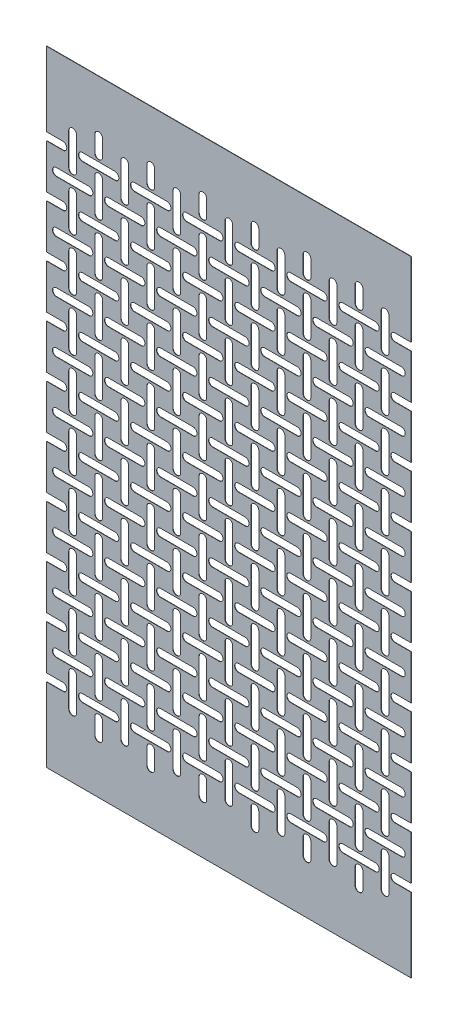
SolidWorks part; units mm, degrees
ref_plane "Front Plane" through (0, 0, 0) normal (0, 0, 1) x (1, 0, 0)
ref_plane "Top Plane" through (0, 0, 0) normal (0, 1, 0) x (1, 0, 0)
ref_plane "Right Plane" through (0, 0, 0) normal (1, 0, 0) x (0, 0, -1)
sketch "Model" plane through (0, 0, 0) normal (0, 0, 1) x (1, 0, 0)
  line L0 (0, 31.5) -> (6.25, 31.5)
  line L1 (0, 28.5) -> (6.25, 28.5)
  line L2 (13.75, 31.5) -> (26.25, 31.5)
  line L3 (13.75, 28.5) -> (26.25, 28.5)
  line L4 (33.75, 31.5) -> (46.25, 31.5)
  line L5 (33.75, 28.5) -> (46.25, 28.5)
  line L6 (53.75, 31.5) -> (66.25, 31.5)
  line L7 (53.75, 28.5) -> (66.25, 28.5)
  line L8 (73.75, 31.5) -> (86.25, 31.5)
  line L9 (73.75, 28.5) -> (86.25, 28.5)
  line L10 (93.75, 31.5) -> (106.25, 31.5)
  line L11 (93.75, 28.5) -> (106.25, 28.5)
  line L12 (113.75, 31.5) -> (126.25, 31.5)
  line L13 (113.75, 28.5) -> (126.25, 28.5)
  line L14 (133.75, 31.5) -> (140, 31.5)
  line L15 (133.75, 28.5) -> (140, 28.5)
  line L16 (3.75, 41.5) -> (16.25, 41.5)
  line L17 (3.75, 38.5) -> (16.25, 38.5)
  line L18 (23.75, 41.5) -> (36.25, 41.5)
  line L19 (23.75, 38.5) -> (36.25, 38.5)
  line L20 (43.75, 41.5) -> (56.25, 41.5)
  line L21 (43.75, 38.5) -> (56.25, 38.5)
  line L22 (63.75, 41.5) -> (76.25, 41.5)
  line L23 (63.75, 38.5) -> (76.25, 38.5)
  line L24 (83.75, 41.5) -> (96.25, 41.5)
  line L25 (83.75, 38.5) -> (96.25, 38.5)
  line L26 (103.75, 41.5) -> (116.25, 41.5)
  line L27 (103.75, 38.5) -> (116.25, 38.5)
  line L28 (123.75, 41.5) -> (136.25, 41.5)
  line L29 (123.75, 38.5) -> (136.25, 38.5)
  line L30 (0, 51.5) -> (6.25, 51.5)
  line L31 (0, 48.5) -> (6.25, 48.5)
  line L32 (13.75, 51.5) -> (26.25, 51.5)
  line L33 (13.75, 48.5) -> (26.25, 48.5)
  line L34 (33.75, 51.5) -> (46.25, 51.5)
  line L35 (33.75, 48.5) -> (46.25, 48.5)
  line L36 (53.75, 51.5) -> (66.25, 51.5)
  line L37 (53.75, 48.5) -> (66.25, 48.5)
  line L38 (73.75, 51.5) -> (86.25, 51.5)
  line L39 (73.75, 48.5) -> (86.25, 48.5)
  line L40 (93.75, 51.5) -> (106.25, 51.5)
  line L41 (93.75, 48.5) -> (106.25, 48.5)
  line L42 (113.75, 51.5) -> (126.25, 51.5)
  line L43 (113.75, 48.5) -> (126.25, 48.5)
  line L44 (133.75, 51.5) -> (140, 51.5)
  line L45 (133.75, 48.5) -> (140, 48.5)
  line L46 (3.75, 61.5) -> (16.25, 61.5)
  line L47 (3.75, 58.5) -> (16.25, 58.5)
  line L48 (23.75, 61.5) -> (36.25, 61.5)
  line L49 (23.75, 58.5) -> (36.25, 58.5)
  line L50 (43.75, 61.5) -> (56.25, 61.5)
  line L51 (43.75, 58.5) -> (56.25, 58.5)
  line L52 (63.75, 61.5) -> (76.25, 61.5)
  line L53 (63.75, 58.5) -> (76.25, 58.5)
  line L54 (83.75, 61.5) -> (96.25, 61.5)
  line L55 (83.75, 58.5) -> (96.25, 58.5)
  line L56 (103.75, 61.5) -> (116.25, 61.5)
  line L57 (103.75, 58.5) -> (116.25, 58.5)
  line L58 (123.75, 61.5) -> (136.25, 61.5)
  line L59 (123.75, 58.5) -> (136.25, 58.5)
  line L60 (0, 71.5) -> (6.25, 71.5)
  line L61 (0, 68.5) -> (6.25, 68.5)
  line L62 (13.75, 71.5) -> (26.25, 71.5)
  line L63 (13.75, 68.5) -> (26.25, 68.5)
  line L64 (33.75, 71.5) -> (46.25, 71.5)
  line L65 (33.75, 68.5) -> (46.25, 68.5)
  line L66 (53.75, 71.5) -> (66.25, 71.5)
  line L67 (53.75, 68.5) -> (66.25, 68.5)
  line L68 (73.75, 71.5) -> (86.25, 71.5)
  line L69 (73.75, 68.5) -> (86.25, 68.5)
  line L70 (93.75, 71.5) -> (106.25, 71.5)
  line L71 (93.75, 68.5) -> (106.25, 68.5)
  line L72 (113.75, 71.5) -> (126.25, 71.5)
  line L73 (113.75, 68.5) -> (126.25, 68.5)
  line L74 (133.75, 71.5) -> (140, 71.5)
  line L75 (133.75, 68.5) -> (140, 68.5)
  line L76 (3.75, 81.5) -> (16.25, 81.5)
  line L77 (3.75, 78.5) -> (16.25, 78.5)
  line L78 (23.75, 81.5) -> (36.25, 81.5)
  line L79 (23.75, 78.5) -> (36.25, 78.5)
  line L80 (43.75, 81.5) -> (56.25, 81.5)
  line L81 (43.75, 78.5) -> (56.25, 78.5)
  line L82 (63.75, 81.5) -> (76.25, 81.5)
  line L83 (63.75, 78.5) -> (76.25, 78.5)
  line L84 (83.75, 81.5) -> (96.25, 81.5)
  line L85 (83.75, 78.5) -> (96.25, 78.5)
  line L86 (103.75, 81.5) -> (116.25, 81.5)
  line L87 (103.75, 78.5) -> (116.25, 78.5)
  line L88 (123.75, 81.5) -> (136.25, 81.5)
  line L89 (123.75, 78.5) -> (136.25, 78.5)
  line L90 (0, 91.5) -> (6.25, 91.5)
  line L91 (0, 88.5) -> (6.25, 88.5)
  line L92 (13.75, 91.5) -> (26.25, 91.5)
  line L93 (13.75, 88.5) -> (26.25, 88.5)
  line L94 (33.75, 91.5) -> (46.25, 91.5)
  line L95 (33.75, 88.5) -> (46.25, 88.5)
  line L96 (53.75, 91.5) -> (66.25, 91.5)
  line L97 (53.75, 88.5) -> (66.25, 88.5)
  line L98 (73.75, 91.5) -> (86.25, 91.5)
  line L99 (73.75, 88.5) -> (86.25, 88.5)
  line L100 (93.75, 91.5) -> (106.25, 91.5)
  line L101 (93.75, 88.5) -> (106.25, 88.5)
  line L102 (113.75, 91.5) -> (126.25, 91.5)
  line L103 (113.75, 88.5) -> (126.25, 88.5)
  line L104 (133.75, 91.5) -> (140, 91.5)
  line L105 (133.75, 88.5) -> (140, 88.5)
  line L106 (3.75, 101.5) -> (16.25, 101.5)
  line L107 (3.75, 98.5) -> (16.25, 98.5)
  line L108 (23.75, 101.5) -> (36.25, 101.5)
  line L109 (23.75, 98.5) -> (36.25, 98.5)
  line L110 (43.75, 101.5) -> (56.25, 101.5)
  line L111 (43.75, 98.5) -> (56.25, 98.5)
  line L112 (63.75, 101.5) -> (76.25, 101.5)
  line L113 (63.75, 98.5) -> (76.25, 98.5)
  line L114 (83.75, 101.5) -> (96.25, 101.5)
  line L115 (83.75, 98.5) -> (96.25, 98.5)
  line L116 (103.75, 101.5) -> (116.25, 101.5)
  line L117 (103.75, 98.5) -> (116.25, 98.5)
  line L118 (123.75, 101.5) -> (136.25, 101.5)
  line L119 (123.75, 98.5) -> (136.25, 98.5)
  line L120 (0, 111.5) -> (6.25, 111.5)
  line L121 (0, 108.5) -> (6.25, 108.5)
  line L122 (13.75, 111.5) -> (26.25, 111.5)
  line L123 (13.75, 108.5) -> (26.25, 108.5)
  line L124 (33.75, 111.5) -> (46.25, 111.5)
  line L125 (33.75, 108.5) -> (46.25, 108.5)
  line L126 (53.75, 111.5) -> (66.25, 111.5)
  line L127 (53.75, 108.5) -> (66.25, 108.5)
  line L128 (73.75, 111.5) -> (86.25, 111.5)
  line L129 (73.75, 108.5) -> (86.25, 108.5)
  line L130 (93.75, 111.5) -> (106.25, 111.5)
  line L131 (93.75, 108.5) -> (106.25, 108.5)
  line L132 (113.75, 111.5) -> (126.25, 111.5)
  line L133 (113.75, 108.5) -> (126.25, 108.5)
  line L134 (133.75, 111.5) -> (140, 111.5)
  line L135 (133.75, 108.5) -> (140, 108.5)
  line L136 (3.75, 121.5) -> (16.25, 121.5)
  line L137 (3.75, 118.5) -> (16.25, 118.5)
  line L138 (23.75, 121.5) -> (36.25, 121.5)
  line L139 (23.75, 118.5) -> (36.25, 118.5)
  line L140 (43.75, 121.5) -> (56.25, 121.5)
  line L141 (43.75, 118.5) -> (56.25, 118.5)
  line L142 (63.75, 121.5) -> (76.25, 121.5)
  line L143 (63.75, 118.5) -> (76.25, 118.5)
  line L144 (83.75, 121.5) -> (96.25, 121.5)
  line L145 (83.75, 118.5) -> (96.25, 118.5)
  line L146 (103.75, 121.5) -> (116.25, 121.5)
  line L147 (103.75, 118.5) -> (116.25, 118.5)
  line L148 (123.75, 121.5) -> (136.25, 121.5)
  line L149 (123.75, 118.5) -> (136.25, 118.5)
  line L150 (0, 131.5) -> (6.25, 131.5)
  line L151 (0, 128.5) -> (6.25, 128.5)
  line L152 (13.75, 131.5) -> (26.25, 131.5)
  line L153 (13.75, 128.5) -> (26.25, 128.5)
  line L154 (33.75, 131.5) -> (46.25, 131.5)
  line L155 (33.75, 128.5) -> (46.25, 128.5)
  line L156 (53.75, 131.5) -> (66.25, 131.5)
  line L157 (53.75, 128.5) -> (66.25, 128.5)
  line L158 (73.75, 131.5) -> (86.25, 131.5)
  line L159 (73.75, 128.5) -> (86.25, 128.5)
  line L160 (93.75, 131.5) -> (106.25, 131.5)
  line L161 (93.75, 128.5) -> (106.25, 128.5)
  line L162 (113.75, 131.5) -> (126.25, 131.5)
  line L163 (113.75, 128.5) -> (126.25, 128.5)
  line L164 (133.75, 131.5) -> (140, 131.5)
  line L165 (133.75, 128.5) -> (140, 128.5)
  line L166 (3.75, 141.5) -> (16.25, 141.5)
  line L167 (3.75, 138.5) -> (16.25, 138.5)
  line L168 (23.75, 141.5) -> (36.25, 141.5)
  line L169 (23.75, 138.5) -> (36.25, 138.5)
  line L170 (43.75, 141.5) -> (56.25, 141.5)
  line L171 (43.75, 138.5) -> (56.25, 138.5)
  line L172 (63.75, 141.5) -> (76.25, 141.5)
  line L173 (63.75, 138.5) -> (76.25, 138.5)
  line L174 (83.75, 141.5) -> (96.25, 141.5)
  line L175 (83.75, 138.5) -> (96.25, 138.5)
  line L176 (103.75, 141.5) -> (116.25, 141.5)
  line L177 (103.75, 138.5) -> (116.25, 138.5)
  line L178 (123.75, 141.5) -> (136.25, 141.5)
  line L179 (123.75, 138.5) -> (136.25, 138.5)
  line L180 (0, 151.5) -> (6.25, 151.5)
  line L181 (0, 148.5) -> (6.25, 148.5)
  line L182 (13.75, 151.5) -> (26.25, 151.5)
  line L183 (13.75, 148.5) -> (26.25, 148.5)
  line L184 (33.75, 151.5) -> (46.25, 151.5)
  line L185 (33.75, 148.5) -> (46.25, 148.5)
  line L186 (53.75, 151.5) -> (66.25, 151.5)
  line L187 (53.75, 148.5) -> (66.25, 148.5)
  line L188 (73.75, 151.5) -> (86.25, 151.5)
  line L189 (73.75, 148.5) -> (86.25, 148.5)
  line L190 (93.75, 151.5) -> (106.25, 151.5)
  line L191 (93.75, 148.5) -> (106.25, 148.5)
  line L192 (113.75, 151.5) -> (126.25, 151.5)
  line L193 (113.75, 148.5) -> (126.25, 148.5)
  line L194 (133.75, 151.5) -> (140, 151.5)
  line L195 (133.75, 148.5) -> (140, 148.5)
  line L196 (3.75, 161.5) -> (16.25, 161.5)
  line L197 (3.75, 158.5) -> (16.25, 158.5)
  line L198 (23.75, 161.5) -> (36.25, 161.5)
  line L199 (23.75, 158.5) -> (36.25, 158.5)
  line L200 (43.75, 161.5) -> (56.25, 161.5)
  line L201 (43.75, 158.5) -> (56.25, 158.5)
  line L202 (63.75, 161.5) -> (76.25, 161.5)
  line L203 (63.75, 158.5) -> (76.25, 158.5)
  line L204 (83.75, 161.5) -> (96.25, 161.5)
  line L205 (83.75, 158.5) -> (96.25, 158.5)
  line L206 (103.75, 161.5) -> (116.25, 161.5)
  line L207 (103.75, 158.5) -> (116.25, 158.5)
  line L208 (123.75, 161.5) -> (136.25, 161.5)
  line L209 (123.75, 158.5) -> (136.25, 158.5)
  line L210 (0, 171.5) -> (6.25, 171.5)
  line L211 (0, 168.5) -> (6.25, 168.5)
  line L212 (13.75, 171.5) -> (26.25, 171.5)
  line L213 (13.75, 168.5) -> (26.25, 168.5)
  line L214 (33.75, 171.5) -> (46.25, 171.5)
  line L215 (33.75, 168.5) -> (46.25, 168.5)
  line L216 (53.75, 171.5) -> (66.25, 171.5)
  line L217 (53.75, 168.5) -> (66.25, 168.5)
  line L218 (73.75, 171.5) -> (86.25, 171.5)
  line L219 (73.75, 168.5) -> (86.25, 168.5)
  line L220 (93.75, 171.5) -> (106.25, 171.5)
  line L221 (93.75, 168.5) -> (106.25, 168.5)
  line L222 (113.75, 171.5) -> (126.25, 171.5)
  line L223 (113.75, 168.5) -> (126.25, 168.5)
  line L224 (133.75, 171.5) -> (140, 171.5)
  line L225 (133.75, 168.5) -> (140, 168.5)
  line L226 (3.75, 181.5) -> (16.25, 181.5)
  line L227 (3.75, 178.5) -> (16.25, 178.5)
  line L228 (23.75, 181.5) -> (36.25, 181.5)
  line L229 (23.75, 178.5) -> (36.25, 178.5)
  line L230 (43.75, 181.5) -> (56.25, 181.5)
  line L231 (43.75, 178.5) -> (56.25, 178.5)
  line L232 (63.75, 181.5) -> (76.25, 181.5)
  line L233 (63.75, 178.5) -> (76.25, 178.5)
  line L234 (83.75, 181.5) -> (96.25, 181.5)
  line L235 (83.75, 178.5) -> (96.25, 178.5)
  line L236 (103.75, 181.5) -> (116.25, 181.5)
  line L237 (103.75, 178.5) -> (116.25, 178.5)
  line L238 (123.75, 181.5) -> (136.25, 181.5)
  line L239 (123.75, 178.5) -> (136.25, 178.5)
  line L240 (0, 191.5) -> (6.25, 191.5)
  line L241 (0, 188.5) -> (6.25, 188.5)
  line L242 (13.75, 191.5) -> (26.25, 191.5)
  line L243 (13.75, 188.5) -> (26.25, 188.5)
  line L244 (33.75, 191.5) -> (46.25, 191.5)
  line L245 (33.75, 188.5) -> (46.25, 188.5)
  line L246 (53.75, 191.5) -> (66.25, 191.5)
  line L247 (53.75, 188.5) -> (66.25, 188.5)
  line L248 (73.75, 191.5) -> (86.25, 191.5)
  line L249 (73.75, 188.5) -> (86.25, 188.5)
  line L250 (93.75, 191.5) -> (106.25, 191.5)
  line L251 (93.75, 188.5) -> (106.25, 188.5)
  line L252 (113.75, 191.5) -> (126.25, 191.5)
  line L253 (113.75, 188.5) -> (126.25, 188.5)
  line L254 (133.75, 191.5) -> (140, 191.5)
  line L255 (133.75, 188.5) -> (140, 188.5)
  line L256 (3.75, 201.5) -> (16.25, 201.5)
  line L257 (3.75, 198.5) -> (16.25, 198.5)
  line L258 (23.75, 201.5) -> (36.25, 201.5)
  line L259 (23.75, 198.5) -> (36.25, 198.5)
  line L260 (43.75, 201.5) -> (56.25, 201.5)
  line L261 (43.75, 198.5) -> (56.25, 198.5)
  line L262 (63.75, 201.5) -> (76.25, 201.5)
  line L263 (63.75, 198.5) -> (76.25, 198.5)
  line L264 (83.75, 201.5) -> (96.25, 201.5)
  line L265 (83.75, 198.5) -> (96.25, 198.5)
  line L266 (103.75, 201.5) -> (116.25, 201.5)
  line L267 (103.75, 198.5) -> (116.25, 198.5)
  line L268 (123.75, 201.5) -> (136.25, 201.5)
  line L269 (123.75, 198.5) -> (136.25, 198.5)
  line L270 (0, 211.5) -> (6.25, 211.5)
  line L271 (0, 208.5) -> (6.25, 208.5)
  line L272 (13.75, 211.5) -> (26.25, 211.5)
  line L273 (13.75, 208.5) -> (26.25, 208.5)
  line L274 (33.75, 211.5) -> (46.25, 211.5)
  line L275 (33.75, 208.5) -> (46.25, 208.5)
  line L276 (53.75, 211.5) -> (66.25, 211.5)
  line L277 (53.75, 208.5) -> (66.25, 208.5)
  line L278 (73.75, 211.5) -> (86.25, 211.5)
  line L279 (73.75, 208.5) -> (86.25, 208.5)
  line L280 (93.75, 211.5) -> (106.25, 211.5)
  line L281 (93.75, 208.5) -> (106.25, 208.5)
  line L282 (113.75, 211.5) -> (126.25, 211.5)
  line L283 (113.75, 208.5) -> (126.25, 208.5)
  line L284 (133.75, 211.5) -> (140, 211.5)
  line L285 (133.75, 208.5) -> (140, 208.5)
  line L286 (11.5, 23.75) -> (11.5, 36.25)
  line L287 (8.5, 23.75) -> (8.5, 36.25)
  line L288 (11.5, 43.75) -> (11.5, 56.25)
  line L289 (8.5, 43.75) -> (8.5, 56.25)
  line L290 (11.5, 63.75) -> (11.5, 76.25)
  line L291 (8.5, 63.75) -> (8.5, 76.25)
  line L292 (11.5, 83.75) -> (11.5, 96.25)
  line L293 (8.5, 83.75) -> (8.5, 96.25)
  line L294 (11.5, 103.75) -> (11.5, 116.25)
  line L295 (8.5, 103.75) -> (8.5, 116.25)
  line L296 (11.5, 123.75) -> (11.5, 136.25)
  line L297 (8.5, 123.75) -> (8.5, 136.25)
  line L298 (11.5, 143.75) -> (11.5, 156.25)
  line L299 (8.5, 143.75) -> (8.5, 156.25)
  line L300 (11.5, 163.75) -> (11.5, 176.25)
  line L301 (8.5, 163.75) -> (8.5, 176.25)
  line L302 (11.5, 183.75) -> (11.5, 196.25)
  line L303 (8.5, 183.75) -> (8.5, 196.25)
  line L304 (11.5, 203.75) -> (11.5, 216.25)
  line L305 (8.5, 203.75) -> (8.5, 216.25)
  line L306 (21.5, 20) -> (21.5, 26.25)
  line L307 (18.5, 20) -> (18.5, 26.25)
  line L308 (21.5, 33.75) -> (21.5, 46.25)
  line L309 (18.5, 33.75) -> (18.5, 46.25)
  line L310 (21.5, 53.75) -> (21.5, 66.25)
  line L311 (18.5, 53.75) -> (18.5, 66.25)
  line L312 (21.5, 73.75) -> (21.5, 86.25)
  line L313 (18.5, 73.75) -> (18.5, 86.25)
  line L314 (21.5, 93.75) -> (21.5, 106.25)
  line L315 (18.5, 93.75) -> (18.5, 106.25)
  line L316 (21.5, 113.75) -> (21.5, 126.25)
  line L317 (18.5, 113.75) -> (18.5, 126.25)
  line L318 (21.5, 133.75) -> (21.5, 146.25)
  line L319 (18.5, 133.75) -> (18.5, 146.25)
  line L320 (21.5, 153.75) -> (21.5, 166.25)
  line L321 (18.5, 153.75) -> (18.5, 166.25)
  line L322 (21.5, 173.75) -> (21.5, 186.25)
  line L323 (18.5, 173.75) -> (18.5, 186.25)
  line L324 (21.5, 193.75) -> (21.5, 206.25)
  line L325 (18.5, 193.75) -> (18.5, 206.25)
  line L326 (21.5, 213.75) -> (21.5, 220)
  line L327 (18.5, 213.75) -> (18.5, 220)
  line L328 (31.5, 23.75) -> (31.5, 36.25)
  line L329 (28.5, 23.75) -> (28.5, 36.25)
  line L330 (31.5, 43.75) -> (31.5, 56.25)
  line L331 (28.5, 43.75) -> (28.5, 56.25)
  line L332 (31.5, 63.75) -> (31.5, 76.25)
  line L333 (28.5, 63.75) -> (28.5, 76.25)
  line L334 (31.5, 83.75) -> (31.5, 96.25)
  line L335 (28.5, 83.75) -> (28.5, 96.25)
  line L336 (31.5, 103.75) -> (31.5, 116.25)
  line L337 (28.5, 103.75) -> (28.5, 116.25)
  line L338 (31.5, 123.75) -> (31.5, 136.25)
  line L339 (28.5, 123.75) -> (28.5, 136.25)
  line L340 (31.5, 143.75) -> (31.5, 156.25)
  line L341 (28.5, 143.75) -> (28.5, 156.25)
  line L342 (31.5, 163.75) -> (31.5, 176.25)
  line L343 (28.5, 163.75) -> (28.5, 176.25)
  line L344 (31.5, 183.75) -> (31.5, 196.25)
  line L345 (28.5, 183.75) -> (28.5, 196.25)
  line L346 (31.5, 203.75) -> (31.5, 216.25)
  line L347 (28.5, 203.75) -> (28.5, 216.25)
  line L348 (41.5, 20) -> (41.5, 26.25)
  line L349 (38.5, 20) -> (38.5, 26.25)
  line L350 (41.5, 33.75) -> (41.5, 46.25)
  line L351 (38.5, 33.75) -> (38.5, 46.25)
  line L352 (41.5, 53.75) -> (41.5, 66.25)
  line L353 (38.5, 53.75) -> (38.5, 66.25)
  line L354 (41.5, 73.75) -> (41.5, 86.25)
  line L355 (38.5, 73.75) -> (38.5, 86.25)
  line L356 (41.5, 93.75) -> (41.5, 106.25)
  line L357 (38.5, 93.75) -> (38.5, 106.25)
  line L358 (41.5, 113.75) -> (41.5, 126.25)
  line L359 (38.5, 113.75) -> (38.5, 126.25)
  line L360 (41.5, 133.75) -> (41.5, 146.25)
  line L361 (38.5, 133.75) -> (38.5, 146.25)
  line L362 (41.5, 153.75) -> (41.5, 166.25)
  line L363 (38.5, 153.75) -> (38.5, 166.25)
  line L364 (41.5, 173.75) -> (41.5, 186.25)
  line L365 (38.5, 173.75) -> (38.5, 186.25)
  line L366 (41.5, 193.75) -> (41.5, 206.25)
  line L367 (38.5, 193.75) -> (38.5, 206.25)
  line L368 (41.5, 213.75) -> (41.5, 220)
  line L369 (38.5, 213.75) -> (38.5, 220)
  line L370 (51.5, 23.75) -> (51.5, 36.25)
  line L371 (48.5, 23.75) -> (48.5, 36.25)
  line L372 (51.5, 43.75) -> (51.5, 56.25)
  line L373 (48.5, 43.75) -> (48.5, 56.25)
  line L374 (51.5, 63.75) -> (51.5, 76.25)
  line L375 (48.5, 63.75) -> (48.5, 76.25)
  line L376 (51.5, 83.75) -> (51.5, 96.25)
  line L377 (48.5, 83.75) -> (48.5, 96.25)
  line L378 (51.5, 103.75) -> (51.5, 116.25)
  line L379 (48.5, 103.75) -> (48.5, 116.25)
  line L380 (51.5, 123.75) -> (51.5, 136.25)
  line L381 (48.5, 123.75) -> (48.5, 136.25)
  line L382 (51.5, 143.75) -> (51.5, 156.25)
  line L383 (48.5, 143.75) -> (48.5, 156.25)
  line L384 (51.5, 163.75) -> (51.5, 176.25)
  line L385 (48.5, 163.75) -> (48.5, 176.25)
  line L386 (51.5, 183.75) -> (51.5, 196.25)
  line L387 (48.5, 183.75) -> (48.5, 196.25)
  line L388 (51.5, 203.75) -> (51.5, 216.25)
  line L389 (48.5, 203.75) -> (48.5, 216.25)
  line L390 (61.5, 20) -> (61.5, 26.25)
  line L391 (58.5, 20) -> (58.5, 26.25)
  line L392 (61.5, 33.75) -> (61.5, 46.25)
  line L393 (58.5, 33.75) -> (58.5, 46.25)
  line L394 (61.5, 53.75) -> (61.5, 66.25)
  line L395 (58.5, 53.75) -> (58.5, 66.25)
  line L396 (61.5, 73.75) -> (61.5, 86.25)
  line L397 (58.5, 73.75) -> (58.5, 86.25)
  line L398 (61.5, 93.75) -> (61.5, 106.25)
  line L399 (58.5, 93.75) -> (58.5, 106.25)
  line L400 (61.5, 113.75) -> (61.5, 126.25)
  line L401 (58.5, 113.75) -> (58.5, 126.25)
  line L402 (61.5, 133.75) -> (61.5, 146.25)
  line L403 (58.5, 133.75) -> (58.5, 146.25)
  line L404 (61.5, 153.75) -> (61.5, 166.25)
  line L405 (58.5, 153.75) -> (58.5, 166.25)
  line L406 (61.5, 173.75) -> (61.5, 186.25)
  line L407 (58.5, 173.75) -> (58.5, 186.25)
  line L408 (61.5, 193.75) -> (61.5, 206.25)
  line L409 (58.5, 193.75) -> (58.5, 206.25)
  line L410 (61.5, 213.75) -> (61.5, 220)
  line L411 (58.5, 213.75) -> (58.5, 220)
  line L412 (71.5, 23.75) -> (71.5, 36.25)
  line L413 (68.5, 23.75) -> (68.5, 36.25)
  line L414 (71.5, 43.75) -> (71.5, 56.25)
  line L415 (68.5, 43.75) -> (68.5, 56.25)
  line L416 (71.5, 63.75) -> (71.5, 76.25)
  line L417 (68.5, 63.75) -> (68.5, 76.25)
  line L418 (71.5, 83.75) -> (71.5, 96.25)
  line L419 (68.5, 83.75) -> (68.5, 96.25)
  line L420 (71.5, 103.75) -> (71.5, 116.25)
  line L421 (68.5, 103.75) -> (68.5, 116.25)
  line L422 (71.5, 123.75) -> (71.5, 136.25)
  line L423 (68.5, 123.75) -> (68.5, 136.25)
  line L424 (71.5, 143.75) -> (71.5, 156.25)
  line L425 (68.5, 143.75) -> (68.5, 156.25)
  line L426 (71.5, 163.75) -> (71.5, 176.25)
  line L427 (68.5, 163.75) -> (68.5, 176.25)
  line L428 (71.5, 183.75) -> (71.5, 196.25)
  line L429 (68.5, 183.75) -> (68.5, 196.25)
  line L430 (71.5, 203.75) -> (71.5, 216.25)
  line L431 (68.5, 203.75) -> (68.5, 216.25)
  line L432 (81.5, 20) -> (81.5, 26.25)
  line L433 (78.5, 20) -> (78.5, 26.25)
  line L434 (81.5, 33.75) -> (81.5, 46.25)
  line L435 (78.5, 33.75) -> (78.5, 46.25)
  line L436 (81.5, 53.75) -> (81.5, 66.25)
  line L437 (78.5, 53.75) -> (78.5, 66.25)
  line L438 (81.5, 73.75) -> (81.5, 86.25)
  line L439 (78.5, 73.75) -> (78.5, 86.25)
  line L440 (81.5, 93.75) -> (81.5, 106.25)
  line L441 (78.5, 93.75) -> (78.5, 106.25)
  line L442 (81.5, 113.75) -> (81.5, 126.25)
  line L443 (78.5, 113.75) -> (78.5, 126.25)
  line L444 (81.5, 133.75) -> (81.5, 146.25)
  line L445 (78.5, 133.75) -> (78.5, 146.25)
  line L446 (81.5, 153.75) -> (81.5, 166.25)
  line L447 (78.5, 153.75) -> (78.5, 166.25)
  line L448 (81.5, 173.75) -> (81.5, 186.25)
  line L449 (78.5, 173.75) -> (78.5, 186.25)
  line L450 (81.5, 193.75) -> (81.5, 206.25)
  line L451 (78.5, 193.75) -> (78.5, 206.25)
  line L452 (81.5, 213.75) -> (81.5, 220)
  line L453 (78.5, 213.75) -> (78.5, 220)
  line L454 (91.5, 23.75) -> (91.5, 36.25)
  line L455 (88.5, 23.75) -> (88.5, 36.25)
  line L456 (91.5, 43.75) -> (91.5, 56.25)
  line L457 (88.5, 43.75) -> (88.5, 56.25)
  line L458 (91.5, 63.75) -> (91.5, 76.25)
  line L459 (88.5, 63.75) -> (88.5, 76.25)
  line L460 (91.5, 83.75) -> (91.5, 96.25)
  line L461 (88.5, 83.75) -> (88.5, 96.25)
  line L462 (91.5, 103.75) -> (91.5, 116.25)
  line L463 (88.5, 103.75) -> (88.5, 116.25)
  line L464 (91.5, 123.75) -> (91.5, 136.25)
  line L465 (88.5, 123.75) -> (88.5, 136.25)
  line L466 (91.5, 143.75) -> (91.5, 156.25)
  line L467 (88.5, 143.75) -> (88.5, 156.25)
  line L468 (91.5, 163.75) -> (91.5, 176.25)
  line L469 (88.5, 163.75) -> (88.5, 176.25)
  line L470 (91.5, 183.75) -> (91.5, 196.25)
  line L471 (88.5, 183.75) -> (88.5, 196.25)
  line L472 (91.5, 203.75) -> (91.5, 216.25)
  line L473 (88.5, 203.75) -> (88.5, 216.25)
  line L474 (101.5, 20) -> (101.5, 26.25)
  line L475 (98.5, 20) -> (98.5, 26.25)
  line L476 (101.5, 33.75) -> (101.5, 46.25)
  line L477 (98.5, 33.75) -> (98.5, 46.25)
  line L478 (101.5, 53.75) -> (101.5, 66.25)
  line L479 (98.5, 53.75) -> (98.5, 66.25)
  line L480 (101.5, 73.75) -> (101.5, 86.25)
  line L481 (98.5, 73.75) -> (98.5, 86.25)
  line L482 (101.5, 93.75) -> (101.5, 106.25)
  line L483 (98.5, 93.75) -> (98.5, 106.25)
  line L484 (101.5, 113.75) -> (101.5, 126.25)
  line L485 (98.5, 113.75) -> (98.5, 126.25)
  line L486 (101.5, 133.75) -> (101.5, 146.25)
  line L487 (98.5, 133.75) -> (98.5, 146.25)
  line L488 (101.5, 153.75) -> (101.5, 166.25)
  line L489 (98.5, 153.75) -> (98.5, 166.25)
  line L490 (101.5, 173.75) -> (101.5, 186.25)
  line L491 (98.5, 173.75) -> (98.5, 186.25)
  line L492 (101.5, 193.75) -> (101.5, 206.25)
  line L493 (98.5, 193.75) -> (98.5, 206.25)
  line L494 (101.5, 213.75) -> (101.5, 220)
  line L495 (98.5, 213.75) -> (98.5, 220)
  line L496 (111.5, 23.75) -> (111.5, 36.25)
  line L497 (108.5, 23.75) -> (108.5, 36.25)
  line L498 (111.5, 43.75) -> (111.5, 56.25)
  line L499 (108.5, 43.75) -> (108.5, 56.25)
  line L500 (111.5, 63.75) -> (111.5, 76.25)
  line L501 (108.5, 63.75) -> (108.5, 76.25)
  line L502 (111.5, 83.75) -> (111.5, 96.25)
  line L503 (108.5, 83.75) -> (108.5, 96.25)
  line L504 (111.5, 103.75) -> (111.5, 116.25)
  line L505 (108.5, 103.75) -> (108.5, 116.25)
  line L506 (111.5, 123.75) -> (111.5, 136.25)
  line L507 (108.5, 123.75) -> (108.5, 136.25)
  line L508 (111.5, 143.75) -> (111.5, 156.25)
  line L509 (108.5, 143.75) -> (108.5, 156.25)
  line L510 (111.5, 163.75) -> (111.5, 176.25)
  line L511 (108.5, 163.75) -> (108.5, 176.25)
  line L512 (111.5, 183.75) -> (111.5, 196.25)
  line L513 (108.5, 183.75) -> (108.5, 196.25)
  line L514 (111.5, 203.75) -> (111.5, 216.25)
  line L515 (108.5, 203.75) -> (108.5, 216.25)
  line L516 (121.5, 20) -> (121.5, 26.25)
  line L517 (118.5, 20) -> (118.5, 26.25)
  line L518 (121.5, 33.75) -> (121.5, 46.25)
  line L519 (118.5, 33.75) -> (118.5, 46.25)
  line L520 (121.5, 53.75) -> (121.5, 66.25)
  line L521 (118.5, 53.75) -> (118.5, 66.25)
  line L522 (121.5, 73.75) -> (121.5, 86.25)
  line L523 (118.5, 73.75) -> (118.5, 86.25)
  line L524 (121.5, 93.75) -> (121.5, 106.25)
  line L525 (118.5, 93.75) -> (118.5, 106.25)
  line L526 (121.5, 113.75) -> (121.5, 126.25)
  line L527 (118.5, 113.75) -> (118.5, 126.25)
  line L528 (121.5, 133.75) -> (121.5, 146.25)
  line L529 (118.5, 133.75) -> (118.5, 146.25)
  line L530 (121.5, 153.75) -> (121.5, 166.25)
  line L531 (118.5, 153.75) -> (118.5, 166.25)
  line L532 (121.5, 173.75) -> (121.5, 186.25)
  line L533 (118.5, 173.75) -> (118.5, 186.25)
  line L534 (121.5, 193.75) -> (121.5, 206.25)
  line L535 (118.5, 193.75) -> (118.5, 206.25)
  line L536 (121.5, 213.75) -> (121.5, 220)
  line L537 (118.5, 213.75) -> (118.5, 220)
  line L538 (131.5, 23.75) -> (131.5, 36.25)
  line L539 (128.5, 23.75) -> (128.5, 36.25)
  line L540 (131.5, 43.75) -> (131.5, 56.25)
  line L541 (128.5, 43.75) -> (128.5, 56.25)
  line L542 (131.5, 63.75) -> (131.5, 76.25)
  line L543 (128.5, 63.75) -> (128.5, 76.25)
  line L544 (131.5, 83.75) -> (131.5, 96.25)
  line L545 (128.5, 83.75) -> (128.5, 96.25)
  line L546 (131.5, 103.75) -> (131.5, 116.25)
  line L547 (128.5, 103.75) -> (128.5, 116.25)
  line L548 (131.5, 123.75) -> (131.5, 136.25)
  line L549 (128.5, 123.75) -> (128.5, 136.25)
  line L550 (131.5, 143.75) -> (131.5, 156.25)
  line L551 (128.5, 143.75) -> (128.5, 156.25)
  line L552 (131.5, 163.75) -> (131.5, 176.25)
  line L553 (128.5, 163.75) -> (128.5, 176.25)
  line L554 (131.5, 183.75) -> (131.5, 196.25)
  line L555 (128.5, 183.75) -> (128.5, 196.25)
  line L556 (131.5, 203.75) -> (131.5, 216.25)
  line L557 (128.5, 203.75) -> (128.5, 216.25)
  line L558 (0, 0) -> (140, 0)
  line L559 (140, 0) -> (140, 28.5)
  line L560 (140, 31.5) -> (140, 48.5)
  line L561 (140, 51.5) -> (140, 68.5)
  line L562 (140, 71.5) -> (140, 88.5)
  line L563 (140, 91.5) -> (140, 108.5)
  line L564 (140, 111.5) -> (140, 128.5)
  line L565 (140, 131.5) -> (140, 148.5)
  line L566 (140, 151.5) -> (140, 168.5)
  line L567 (140, 171.5) -> (140, 188.5)
  line L568 (140, 191.5) -> (140, 208.5)
  line L569 (140, 211.5) -> (140, 240)
  line L570 (140, 240) -> (0, 240)
  line L571 (0, 0) -> (0, 28.5)
  line L572 (0, 31.5) -> (0, 48.5)
  line L573 (0, 51.5) -> (0, 68.5)
  line L574 (0, 71.5) -> (0, 88.5)
  line L575 (0, 91.5) -> (0, 108.5)
  line L576 (0, 111.5) -> (0, 128.5)
  line L577 (0, 131.5) -> (0, 148.5)
  line L578 (0, 151.5) -> (0, 168.5)
  line L579 (0, 171.5) -> (0, 188.5)
  line L580 (0, 191.5) -> (0, 208.5)
  line L581 (0, 211.5) -> (0, 240)
  arc A0 (6.25, 28.5) -> (6.25, 31.5) centre (6.25, 30) ccw
  arc A1 (13.75, 31.5) -> (13.75, 28.5) centre (13.75, 30) ccw
  arc A2 (26.25, 28.5) -> (26.25, 31.5) centre (26.25, 30) ccw
  arc A3 (33.75, 31.5) -> (33.75, 28.5) centre (33.75, 30) ccw
  arc A4 (46.25, 28.5) -> (46.25, 31.5) centre (46.25, 30) ccw
  arc A5 (53.75, 31.5) -> (53.75, 28.5) centre (53.75, 30) ccw
  arc A6 (66.25, 28.5) -> (66.25, 31.5) centre (66.25, 30) ccw
  arc A7 (73.75, 31.5) -> (73.75, 28.5) centre (73.75, 30) ccw
  arc A8 (86.25, 28.5) -> (86.25, 31.5) centre (86.25, 30) ccw
  arc A9 (93.75, 31.5) -> (93.75, 28.5) centre (93.75, 30) ccw
  arc A10 (106.25, 28.5) -> (106.25, 31.5) centre (106.25, 30) ccw
  arc A11 (113.75, 31.5) -> (113.75, 28.5) centre (113.75, 30) ccw
  arc A12 (126.25, 28.5) -> (126.25, 31.5) centre (126.25, 30) ccw
  arc A13 (133.75, 31.5) -> (133.75, 28.5) centre (133.75, 30) ccw
  arc A14 (3.75, 41.5) -> (3.75, 38.5) centre (3.75, 40) ccw
  arc A15 (16.25, 38.5) -> (16.25, 41.5) centre (16.25, 40) ccw
  arc A16 (23.75, 41.5) -> (23.75, 38.5) centre (23.75, 40) ccw
  arc A17 (36.25, 38.5) -> (36.25, 41.5) centre (36.25, 40) ccw
  arc A18 (43.75, 41.5) -> (43.75, 38.5) centre (43.75, 40) ccw
  arc A19 (56.25, 38.5) -> (56.25, 41.5) centre (56.25, 40) ccw
  arc A20 (63.75, 41.5) -> (63.75, 38.5) centre (63.75, 40) ccw
  arc A21 (76.25, 38.5) -> (76.25, 41.5) centre (76.25, 40) ccw
  arc A22 (83.75, 41.5) -> (83.75, 38.5) centre (83.75, 40) ccw
  arc A23 (96.25, 38.5) -> (96.25, 41.5) centre (96.25, 40) ccw
  arc A24 (103.75, 41.5) -> (103.75, 38.5) centre (103.75, 40) ccw
  arc A25 (116.25, 38.5) -> (116.25, 41.5) centre (116.25, 40) ccw
  arc A26 (123.75, 41.5) -> (123.75, 38.5) centre (123.75, 40) ccw
  arc A27 (136.25, 38.5) -> (136.25, 41.5) centre (136.25, 40) ccw
  arc A28 (6.25, 48.5) -> (6.25, 51.5) centre (6.25, 50) ccw
  arc A29 (13.75, 51.5) -> (13.75, 48.5) centre (13.75, 50) ccw
  arc A30 (26.25, 48.5) -> (26.25, 51.5) centre (26.25, 50) ccw
  arc A31 (33.75, 51.5) -> (33.75, 48.5) centre (33.75, 50) ccw
  arc A32 (46.25, 48.5) -> (46.25, 51.5) centre (46.25, 50) ccw
  arc A33 (53.75, 51.5) -> (53.75, 48.5) centre (53.75, 50) ccw
  arc A34 (66.25, 48.5) -> (66.25, 51.5) centre (66.25, 50) ccw
  arc A35 (73.75, 51.5) -> (73.75, 48.5) centre (73.75, 50) ccw
  arc A36 (86.25, 48.5) -> (86.25, 51.5) centre (86.25, 50) ccw
  arc A37 (93.75, 51.5) -> (93.75, 48.5) centre (93.75, 50) ccw
  arc A38 (106.25, 48.5) -> (106.25, 51.5) centre (106.25, 50) ccw
  arc A39 (113.75, 51.5) -> (113.75, 48.5) centre (113.75, 50) ccw
  arc A40 (126.25, 48.5) -> (126.25, 51.5) centre (126.25, 50) ccw
  arc A41 (133.75, 51.5) -> (133.75, 48.5) centre (133.75, 50) ccw
  arc A42 (3.75, 61.5) -> (3.75, 58.5) centre (3.75, 60) ccw
  arc A43 (16.25, 58.5) -> (16.25, 61.5) centre (16.25, 60) ccw
  arc A44 (23.75, 61.5) -> (23.75, 58.5) centre (23.75, 60) ccw
  arc A45 (36.25, 58.5) -> (36.25, 61.5) centre (36.25, 60) ccw
  arc A46 (43.75, 61.5) -> (43.75, 58.5) centre (43.75, 60) ccw
  arc A47 (56.25, 58.5) -> (56.25, 61.5) centre (56.25, 60) ccw
  arc A48 (63.75, 61.5) -> (63.75, 58.5) centre (63.75, 60) ccw
  arc A49 (76.25, 58.5) -> (76.25, 61.5) centre (76.25, 60) ccw
  arc A50 (83.75, 61.5) -> (83.75, 58.5) centre (83.75, 60) ccw
  arc A51 (96.25, 58.5) -> (96.25, 61.5) centre (96.25, 60) ccw
  arc A52 (103.75, 61.5) -> (103.75, 58.5) centre (103.75, 60) ccw
  arc A53 (116.25, 58.5) -> (116.25, 61.5) centre (116.25, 60) ccw
  arc A54 (123.75, 61.5) -> (123.75, 58.5) centre (123.75, 60) ccw
  arc A55 (136.25, 58.5) -> (136.25, 61.5) centre (136.25, 60) ccw
  arc A56 (6.25, 68.5) -> (6.25, 71.5) centre (6.25, 70) ccw
  arc A57 (13.75, 71.5) -> (13.75, 68.5) centre (13.75, 70) ccw
  arc A58 (26.25, 68.5) -> (26.25, 71.5) centre (26.25, 70) ccw
  arc A59 (33.75, 71.5) -> (33.75, 68.5) centre (33.75, 70) ccw
  arc A60 (46.25, 68.5) -> (46.25, 71.5) centre (46.25, 70) ccw
  arc A61 (53.75, 71.5) -> (53.75, 68.5) centre (53.75, 70) ccw
  arc A62 (66.25, 68.5) -> (66.25, 71.5) centre (66.25, 70) ccw
  arc A63 (73.75, 71.5) -> (73.75, 68.5) centre (73.75, 70) ccw
  arc A64 (86.25, 68.5) -> (86.25, 71.5) centre (86.25, 70) ccw
  arc A65 (93.75, 71.5) -> (93.75, 68.5) centre (93.75, 70) ccw
  arc A66 (106.25, 68.5) -> (106.25, 71.5) centre (106.25, 70) ccw
  arc A67 (113.75, 71.5) -> (113.75, 68.5) centre (113.75, 70) ccw
  arc A68 (126.25, 68.5) -> (126.25, 71.5) centre (126.25, 70) ccw
  arc A69 (133.75, 71.5) -> (133.75, 68.5) centre (133.75, 70) ccw
  arc A70 (3.75, 81.5) -> (3.75, 78.5) centre (3.75, 80) ccw
  arc A71 (16.25, 78.5) -> (16.25, 81.5) centre (16.25, 80) ccw
  arc A72 (23.75, 81.5) -> (23.75, 78.5) centre (23.75, 80) ccw
  arc A73 (36.25, 78.5) -> (36.25, 81.5) centre (36.25, 80) ccw
  arc A74 (43.75, 81.5) -> (43.75, 78.5) centre (43.75, 80) ccw
  arc A75 (56.25, 78.5) -> (56.25, 81.5) centre (56.25, 80) ccw
  arc A76 (63.75, 81.5) -> (63.75, 78.5) centre (63.75, 80) ccw
  arc A77 (76.25, 78.5) -> (76.25, 81.5) centre (76.25, 80) ccw
  arc A78 (83.75, 81.5) -> (83.75, 78.5) centre (83.75, 80) ccw
  arc A79 (96.25, 78.5) -> (96.25, 81.5) centre (96.25, 80) ccw
  arc A80 (103.75, 81.5) -> (103.75, 78.5) centre (103.75, 80) ccw
  arc A81 (116.25, 78.5) -> (116.25, 81.5) centre (116.25, 80) ccw
  arc A82 (123.75, 81.5) -> (123.75, 78.5) centre (123.75, 80) ccw
  arc A83 (136.25, 78.5) -> (136.25, 81.5) centre (136.25, 80) ccw
  arc A84 (6.25, 88.5) -> (6.25, 91.5) centre (6.25, 90) ccw
  arc A85 (13.75, 91.5) -> (13.75, 88.5) centre (13.75, 90) ccw
  arc A86 (26.25, 88.5) -> (26.25, 91.5) centre (26.25, 90) ccw
  arc A87 (33.75, 91.5) -> (33.75, 88.5) centre (33.75, 90) ccw
  arc A88 (46.25, 88.5) -> (46.25, 91.5) centre (46.25, 90) ccw
  arc A89 (53.75, 91.5) -> (53.75, 88.5) centre (53.75, 90) ccw
  arc A90 (66.25, 88.5) -> (66.25, 91.5) centre (66.25, 90) ccw
  arc A91 (73.75, 91.5) -> (73.75, 88.5) centre (73.75, 90) ccw
  arc A92 (86.25, 88.5) -> (86.25, 91.5) centre (86.25, 90) ccw
  arc A93 (93.75, 91.5) -> (93.75, 88.5) centre (93.75, 90) ccw
  arc A94 (106.25, 88.5) -> (106.25, 91.5) centre (106.25, 90) ccw
  arc A95 (113.75, 91.5) -> (113.75, 88.5) centre (113.75, 90) ccw
  arc A96 (126.25, 88.5) -> (126.25, 91.5) centre (126.25, 90) ccw
  arc A97 (133.75, 91.5) -> (133.75, 88.5) centre (133.75, 90) ccw
  arc A98 (3.75, 101.5) -> (3.75, 98.5) centre (3.75, 100) ccw
  arc A99 (16.25, 98.5) -> (16.25, 101.5) centre (16.25, 100) ccw
  arc A100 (23.75, 101.5) -> (23.75, 98.5) centre (23.75, 100) ccw
  arc A101 (36.25, 98.5) -> (36.25, 101.5) centre (36.25, 100) ccw
  arc A102 (43.75, 101.5) -> (43.75, 98.5) centre (43.75, 100) ccw
  arc A103 (56.25, 98.5) -> (56.25, 101.5) centre (56.25, 100) ccw
  arc A104 (63.75, 101.5) -> (63.75, 98.5) centre (63.75, 100) ccw
  arc A105 (76.25, 98.5) -> (76.25, 101.5) centre (76.25, 100) ccw
  arc A106 (83.75, 101.5) -> (83.75, 98.5) centre (83.75, 100) ccw
  arc A107 (96.25, 98.5) -> (96.25, 101.5) centre (96.25, 100) ccw
  arc A108 (103.75, 101.5) -> (103.75, 98.5) centre (103.75, 100) ccw
  arc A109 (116.25, 98.5) -> (116.25, 101.5) centre (116.25, 100) ccw
  arc A110 (123.75, 101.5) -> (123.75, 98.5) centre (123.75, 100) ccw
  arc A111 (136.25, 98.5) -> (136.25, 101.5) centre (136.25, 100) ccw
  arc A112 (6.25, 108.5) -> (6.25, 111.5) centre (6.25, 110) ccw
  arc A113 (13.75, 111.5) -> (13.75, 108.5) centre (13.75, 110) ccw
  arc A114 (26.25, 108.5) -> (26.25, 111.5) centre (26.25, 110) ccw
  arc A115 (33.75, 111.5) -> (33.75, 108.5) centre (33.75, 110) ccw
  arc A116 (46.25, 108.5) -> (46.25, 111.5) centre (46.25, 110) ccw
  arc A117 (53.75, 111.5) -> (53.75, 108.5) centre (53.75, 110) ccw
  arc A118 (66.25, 108.5) -> (66.25, 111.5) centre (66.25, 110) ccw
  arc A119 (73.75, 111.5) -> (73.75, 108.5) centre (73.75, 110) ccw
  arc A120 (86.25, 108.5) -> (86.25, 111.5) centre (86.25, 110) ccw
  arc A121 (93.75, 111.5) -> (93.75, 108.5) centre (93.75, 110) ccw
  arc A122 (106.25, 108.5) -> (106.25, 111.5) centre (106.25, 110) ccw
  arc A123 (113.75, 111.5) -> (113.75, 108.5) centre (113.75, 110) ccw
  arc A124 (126.25, 108.5) -> (126.25, 111.5) centre (126.25, 110) ccw
  arc A125 (133.75, 111.5) -> (133.75, 108.5) centre (133.75, 110) ccw
  arc A126 (3.75, 121.5) -> (3.75, 118.5) centre (3.75, 120) ccw
  arc A127 (16.25, 118.5) -> (16.25, 121.5) centre (16.25, 120) ccw
  arc A128 (23.75, 121.5) -> (23.75, 118.5) centre (23.75, 120) ccw
  arc A129 (36.25, 118.5) -> (36.25, 121.5) centre (36.25, 120) ccw
  arc A130 (43.75, 121.5) -> (43.75, 118.5) centre (43.75, 120) ccw
  arc A131 (56.25, 118.5) -> (56.25, 121.5) centre (56.25, 120) ccw
  arc A132 (63.75, 121.5) -> (63.75, 118.5) centre (63.75, 120) ccw
  arc A133 (76.25, 118.5) -> (76.25, 121.5) centre (76.25, 120) ccw
  arc A134 (83.75, 121.5) -> (83.75, 118.5) centre (83.75, 120) ccw
  arc A135 (96.25, 118.5) -> (96.25, 121.5) centre (96.25, 120) ccw
  arc A136 (103.75, 121.5) -> (103.75, 118.5) centre (103.75, 120) ccw
  arc A137 (116.25, 118.5) -> (116.25, 121.5) centre (116.25, 120) ccw
  arc A138 (123.75, 121.5) -> (123.75, 118.5) centre (123.75, 120) ccw
  arc A139 (136.25, 118.5) -> (136.25, 121.5) centre (136.25, 120) ccw
  arc A140 (6.25, 128.5) -> (6.25, 131.5) centre (6.25, 130) ccw
  arc A141 (13.75, 131.5) -> (13.75, 128.5) centre (13.75, 130) ccw
  arc A142 (26.25, 128.5) -> (26.25, 131.5) centre (26.25, 130) ccw
  arc A143 (33.75, 131.5) -> (33.75, 128.5) centre (33.75, 130) ccw
  arc A144 (46.25, 128.5) -> (46.25, 131.5) centre (46.25, 130) ccw
  arc A145 (53.75, 131.5) -> (53.75, 128.5) centre (53.75, 130) ccw
  arc A146 (66.25, 128.5) -> (66.25, 131.5) centre (66.25, 130) ccw
  arc A147 (73.75, 131.5) -> (73.75, 128.5) centre (73.75, 130) ccw
  arc A148 (86.25, 128.5) -> (86.25, 131.5) centre (86.25, 130) ccw
  arc A149 (93.75, 131.5) -> (93.75, 128.5) centre (93.75, 130) ccw
  arc A150 (106.25, 128.5) -> (106.25, 131.5) centre (106.25, 130) ccw
  arc A151 (113.75, 131.5) -> (113.75, 128.5) centre (113.75, 130) ccw
  arc A152 (126.25, 128.5) -> (126.25, 131.5) centre (126.25, 130) ccw
  arc A153 (133.75, 131.5) -> (133.75, 128.5) centre (133.75, 130) ccw
  arc A154 (3.75, 141.5) -> (3.75, 138.5) centre (3.75, 140) ccw
  arc A155 (16.25, 138.5) -> (16.25, 141.5) centre (16.25, 140) ccw
  arc A156 (23.75, 141.5) -> (23.75, 138.5) centre (23.75, 140) ccw
  arc A157 (36.25, 138.5) -> (36.25, 141.5) centre (36.25, 140) ccw
  arc A158 (43.75, 141.5) -> (43.75, 138.5) centre (43.75, 140) ccw
  arc A159 (56.25, 138.5) -> (56.25, 141.5) centre (56.25, 140) ccw
  arc A160 (63.75, 141.5) -> (63.75, 138.5) centre (63.75, 140) ccw
  arc A161 (76.25, 138.5) -> (76.25, 141.5) centre (76.25, 140) ccw
  arc A162 (83.75, 141.5) -> (83.75, 138.5) centre (83.75, 140) ccw
  arc A163 (96.25, 138.5) -> (96.25, 141.5) centre (96.25, 140) ccw
  arc A164 (103.75, 141.5) -> (103.75, 138.5) centre (103.75, 140) ccw
  arc A165 (116.25, 138.5) -> (116.25, 141.5) centre (116.25, 140) ccw
  arc A166 (123.75, 141.5) -> (123.75, 138.5) centre (123.75, 140) ccw
  arc A167 (136.25, 138.5) -> (136.25, 141.5) centre (136.25, 140) ccw
  arc A168 (6.25, 148.5) -> (6.25, 151.5) centre (6.25, 150) ccw
  arc A169 (13.75, 151.5) -> (13.75, 148.5) centre (13.75, 150) ccw
  arc A170 (26.25, 148.5) -> (26.25, 151.5) centre (26.25, 150) ccw
  arc A171 (33.75, 151.5) -> (33.75, 148.5) centre (33.75, 150) ccw
  arc A172 (46.25, 148.5) -> (46.25, 151.5) centre (46.25, 150) ccw
  arc A173 (53.75, 151.5) -> (53.75, 148.5) centre (53.75, 150) ccw
  arc A174 (66.25, 148.5) -> (66.25, 151.5) centre (66.25, 150) ccw
  arc A175 (73.75, 151.5) -> (73.75, 148.5) centre (73.75, 150) ccw
  arc A176 (86.25, 148.5) -> (86.25, 151.5) centre (86.25, 150) ccw
  arc A177 (93.75, 151.5) -> (93.75, 148.5) centre (93.75, 150) ccw
  arc A178 (106.25, 148.5) -> (106.25, 151.5) centre (106.25, 150) ccw
  arc A179 (113.75, 151.5) -> (113.75, 148.5) centre (113.75, 150) ccw
  arc A180 (126.25, 148.5) -> (126.25, 151.5) centre (126.25, 150) ccw
  arc A181 (133.75, 151.5) -> (133.75, 148.5) centre (133.75, 150) ccw
  arc A182 (3.75, 161.5) -> (3.75, 158.5) centre (3.75, 160) ccw
  arc A183 (16.25, 158.5) -> (16.25, 161.5) centre (16.25, 160) ccw
  arc A184 (23.75, 161.5) -> (23.75, 158.5) centre (23.75, 160) ccw
  arc A185 (36.25, 158.5) -> (36.25, 161.5) centre (36.25, 160) ccw
  arc A186 (43.75, 161.5) -> (43.75, 158.5) centre (43.75, 160) ccw
  arc A187 (56.25, 158.5) -> (56.25, 161.5) centre (56.25, 160) ccw
  arc A188 (63.75, 161.5) -> (63.75, 158.5) centre (63.75, 160) ccw
  arc A189 (76.25, 158.5) -> (76.25, 161.5) centre (76.25, 160) ccw
  arc A190 (83.75, 161.5) -> (83.75, 158.5) centre (83.75, 160) ccw
  arc A191 (96.25, 158.5) -> (96.25, 161.5) centre (96.25, 160) ccw
  arc A192 (103.75, 161.5) -> (103.75, 158.5) centre (103.75, 160) ccw
  arc A193 (116.25, 158.5) -> (116.25, 161.5) centre (116.25, 160) ccw
  arc A194 (123.75, 161.5) -> (123.75, 158.5) centre (123.75, 160) ccw
  arc A195 (136.25, 158.5) -> (136.25, 161.5) centre (136.25, 160) ccw
  arc A196 (6.25, 168.5) -> (6.25, 171.5) centre (6.25, 170) ccw
  arc A197 (13.75, 171.5) -> (13.75, 168.5) centre (13.75, 170) ccw
  arc A198 (26.25, 168.5) -> (26.25, 171.5) centre (26.25, 170) ccw
  arc A199 (33.75, 171.5) -> (33.75, 168.5) centre (33.75, 170) ccw
  arc A200 (46.25, 168.5) -> (46.25, 171.5) centre (46.25, 170) ccw
  arc A201 (53.75, 171.5) -> (53.75, 168.5) centre (53.75, 170) ccw
  arc A202 (66.25, 168.5) -> (66.25, 171.5) centre (66.25, 170) ccw
  arc A203 (73.75, 171.5) -> (73.75, 168.5) centre (73.75, 170) ccw
  arc A204 (86.25, 168.5) -> (86.25, 171.5) centre (86.25, 170) ccw
  arc A205 (93.75, 171.5) -> (93.75, 168.5) centre (93.75, 170) ccw
  arc A206 (106.25, 168.5) -> (106.25, 171.5) centre (106.25, 170) ccw
  arc A207 (113.75, 171.5) -> (113.75, 168.5) centre (113.75, 170) ccw
  arc A208 (126.25, 168.5) -> (126.25, 171.5) centre (126.25, 170) ccw
  arc A209 (133.75, 171.5) -> (133.75, 168.5) centre (133.75, 170) ccw
  arc A210 (3.75, 181.5) -> (3.75, 178.5) centre (3.75, 180) ccw
  arc A211 (16.25, 178.5) -> (16.25, 181.5) centre (16.25, 180) ccw
  arc A212 (23.75, 181.5) -> (23.75, 178.5) centre (23.75, 180) ccw
  arc A213 (36.25, 178.5) -> (36.25, 181.5) centre (36.25, 180) ccw
  arc A214 (43.75, 181.5) -> (43.75, 178.5) centre (43.75, 180) ccw
  arc A215 (56.25, 178.5) -> (56.25, 181.5) centre (56.25, 180) ccw
  arc A216 (63.75, 181.5) -> (63.75, 178.5) centre (63.75, 180) ccw
  arc A217 (76.25, 178.5) -> (76.25, 181.5) centre (76.25, 180) ccw
  arc A218 (83.75, 181.5) -> (83.75, 178.5) centre (83.75, 180) ccw
  arc A219 (96.25, 178.5) -> (96.25, 181.5) centre (96.25, 180) ccw
  arc A220 (103.75, 181.5) -> (103.75, 178.5) centre (103.75, 180) ccw
  arc A221 (116.25, 178.5) -> (116.25, 181.5) centre (116.25, 180) ccw
  arc A222 (123.75, 181.5) -> (123.75, 178.5) centre (123.75, 180) ccw
  arc A223 (136.25, 178.5) -> (136.25, 181.5) centre (136.25, 180) ccw
  arc A224 (6.25, 188.5) -> (6.25, 191.5) centre (6.25, 190) ccw
  arc A225 (13.75, 191.5) -> (13.75, 188.5) centre (13.75, 190) ccw
  arc A226 (26.25, 188.5) -> (26.25, 191.5) centre (26.25, 190) ccw
  arc A227 (33.75, 191.5) -> (33.75, 188.5) centre (33.75, 190) ccw
  arc A228 (46.25, 188.5) -> (46.25, 191.5) centre (46.25, 190) ccw
  arc A229 (53.75, 191.5) -> (53.75, 188.5) centre (53.75, 190) ccw
  arc A230 (66.25, 188.5) -> (66.25, 191.5) centre (66.25, 190) ccw
  arc A231 (73.75, 191.5) -> (73.75, 188.5) centre (73.75, 190) ccw
  arc A232 (86.25, 188.5) -> (86.25, 191.5) centre (86.25, 190) ccw
  arc A233 (93.75, 191.5) -> (93.75, 188.5) centre (93.75, 190) ccw
  arc A234 (106.25, 188.5) -> (106.25, 191.5) centre (106.25, 190) ccw
  arc A235 (113.75, 191.5) -> (113.75, 188.5) centre (113.75, 190) ccw
  arc A236 (126.25, 188.5) -> (126.25, 191.5) centre (126.25, 190) ccw
  arc A237 (133.75, 191.5) -> (133.75, 188.5) centre (133.75, 190) ccw
  arc A238 (3.75, 201.5) -> (3.75, 198.5) centre (3.75, 200) ccw
  arc A239 (16.25, 198.5) -> (16.25, 201.5) centre (16.25, 200) ccw
  arc A240 (23.75, 201.5) -> (23.75, 198.5) centre (23.75, 200) ccw
  arc A241 (36.25, 198.5) -> (36.25, 201.5) centre (36.25, 200) ccw
  arc A242 (43.75, 201.5) -> (43.75, 198.5) centre (43.75, 200) ccw
  arc A243 (56.25, 198.5) -> (56.25, 201.5) centre (56.25, 200) ccw
  arc A244 (63.75, 201.5) -> (63.75, 198.5) centre (63.75, 200) ccw
  arc A245 (76.25, 198.5) -> (76.25, 201.5) centre (76.25, 200) ccw
  arc A246 (83.75, 201.5) -> (83.75, 198.5) centre (83.75, 200) ccw
  arc A247 (96.25, 198.5) -> (96.25, 201.5) centre (96.25, 200) ccw
  arc A248 (103.75, 201.5) -> (103.75, 198.5) centre (103.75, 200) ccw
  arc A249 (116.25, 198.5) -> (116.25, 201.5) centre (116.25, 200) ccw
  arc A250 (123.75, 201.5) -> (123.75, 198.5) centre (123.75, 200) ccw
  arc A251 (136.25, 198.5) -> (136.25, 201.5) centre (136.25, 200) ccw
  arc A252 (6.25, 208.5) -> (6.25, 211.5) centre (6.25, 210) ccw
  arc A253 (13.75, 211.5) -> (13.75, 208.5) centre (13.75, 210) ccw
  arc A254 (26.25, 208.5) -> (26.25, 211.5) centre (26.25, 210) ccw
  arc A255 (33.75, 211.5) -> (33.75, 208.5) centre (33.75, 210) ccw
  arc A256 (46.25, 208.5) -> (46.25, 211.5) centre (46.25, 210) ccw
  arc A257 (53.75, 211.5) -> (53.75, 208.5) centre (53.75, 210) ccw
  arc A258 (66.25, 208.5) -> (66.25, 211.5) centre (66.25, 210) ccw
  arc A259 (73.75, 211.5) -> (73.75, 208.5) centre (73.75, 210) ccw
  arc A260 (86.25, 208.5) -> (86.25, 211.5) centre (86.25, 210) ccw
  arc A261 (93.75, 211.5) -> (93.75, 208.5) centre (93.75, 210) ccw
  arc A262 (106.25, 208.5) -> (106.25, 211.5) centre (106.25, 210) ccw
  arc A263 (113.75, 211.5) -> (113.75, 208.5) centre (113.75, 210) ccw
  arc A264 (126.25, 208.5) -> (126.25, 211.5) centre (126.25, 210) ccw
  arc A265 (133.75, 211.5) -> (133.75, 208.5) centre (133.75, 210) ccw
  arc A266 (8.5, 23.75) -> (11.5, 23.75) centre (10, 23.75) ccw
  arc A267 (11.5, 36.25) -> (8.5, 36.25) centre (10, 36.25) ccw
  arc A268 (8.5, 43.75) -> (11.5, 43.75) centre (10, 43.75) ccw
  arc A269 (11.5, 56.25) -> (8.5, 56.25) centre (10, 56.25) ccw
  arc A270 (8.5, 63.75) -> (11.5, 63.75) centre (10, 63.75) ccw
  arc A271 (11.5, 76.25) -> (8.5, 76.25) centre (10, 76.25) ccw
  arc A272 (8.5, 83.75) -> (11.5, 83.75) centre (10, 83.75) ccw
  arc A273 (11.5, 96.25) -> (8.5, 96.25) centre (10, 96.25) ccw
  arc A274 (8.5, 103.75) -> (11.5, 103.75) centre (10, 103.75) ccw
  arc A275 (11.5, 116.25) -> (8.5, 116.25) centre (10, 116.25) ccw
  arc A276 (8.5, 123.75) -> (11.5, 123.75) centre (10, 123.75) ccw
  arc A277 (11.5, 136.25) -> (8.5, 136.25) centre (10, 136.25) ccw
  arc A278 (8.5, 143.75) -> (11.5, 143.75) centre (10, 143.75) ccw
  arc A279 (11.5, 156.25) -> (8.5, 156.25) centre (10, 156.25) ccw
  arc A280 (8.5, 163.75) -> (11.5, 163.75) centre (10, 163.75) ccw
  arc A281 (11.5, 176.25) -> (8.5, 176.25) centre (10, 176.25) ccw
  arc A282 (8.5, 183.75) -> (11.5, 183.75) centre (10, 183.75) ccw
  arc A283 (11.5, 196.25) -> (8.5, 196.25) centre (10, 196.25) ccw
  arc A284 (8.5, 203.75) -> (11.5, 203.75) centre (10, 203.75) ccw
  arc A285 (11.5, 216.25) -> (8.5, 216.25) centre (10, 216.25) ccw
  arc A286 (18.5, 20) -> (21.5, 20) centre (20, 20) ccw
  arc A287 (21.5, 26.25) -> (18.5, 26.25) centre (20, 26.25) ccw
  arc A288 (18.5, 33.75) -> (21.5, 33.75) centre (20, 33.75) ccw
  arc A289 (21.5, 46.25) -> (18.5, 46.25) centre (20, 46.25) ccw
  arc A290 (18.5, 53.75) -> (21.5, 53.75) centre (20, 53.75) ccw
  arc A291 (21.5, 66.25) -> (18.5, 66.25) centre (20, 66.25) ccw
  arc A292 (18.5, 73.75) -> (21.5, 73.75) centre (20, 73.75) ccw
  arc A293 (21.5, 86.25) -> (18.5, 86.25) centre (20, 86.25) ccw
  arc A294 (18.5, 93.75) -> (21.5, 93.75) centre (20, 93.75) ccw
  arc A295 (21.5, 106.25) -> (18.5, 106.25) centre (20, 106.25) ccw
  arc A296 (18.5, 113.75) -> (21.5, 113.75) centre (20, 113.75) ccw
  arc A297 (21.5, 126.25) -> (18.5, 126.25) centre (20, 126.25) ccw
  arc A298 (18.5, 133.75) -> (21.5, 133.75) centre (20, 133.75) ccw
  arc A299 (21.5, 146.25) -> (18.5, 146.25) centre (20, 146.25) ccw
  arc A300 (18.5, 153.75) -> (21.5, 153.75) centre (20, 153.75) ccw
  arc A301 (21.5, 166.25) -> (18.5, 166.25) centre (20, 166.25) ccw
  arc A302 (18.5, 173.75) -> (21.5, 173.75) centre (20, 173.75) ccw
  arc A303 (21.5, 186.25) -> (18.5, 186.25) centre (20, 186.25) ccw
  arc A304 (18.5, 193.75) -> (21.5, 193.75) centre (20, 193.75) ccw
  arc A305 (21.5, 206.25) -> (18.5, 206.25) centre (20, 206.25) ccw
  arc A306 (18.5, 213.75) -> (21.5, 213.75) centre (20, 213.75) ccw
  arc A307 (21.5, 220) -> (18.5, 220) centre (20, 220) ccw
  arc A308 (28.5, 23.75) -> (31.5, 23.75) centre (30, 23.75) ccw
  arc A309 (31.5, 36.25) -> (28.5, 36.25) centre (30, 36.25) ccw
  arc A310 (28.5, 43.75) -> (31.5, 43.75) centre (30, 43.75) ccw
  arc A311 (31.5, 56.25) -> (28.5, 56.25) centre (30, 56.25) ccw
  arc A312 (28.5, 63.75) -> (31.5, 63.75) centre (30, 63.75) ccw
  arc A313 (31.5, 76.25) -> (28.5, 76.25) centre (30, 76.25) ccw
  arc A314 (28.5, 83.75) -> (31.5, 83.75) centre (30, 83.75) ccw
  arc A315 (31.5, 96.25) -> (28.5, 96.25) centre (30, 96.25) ccw
  arc A316 (28.5, 103.75) -> (31.5, 103.75) centre (30, 103.75) ccw
  arc A317 (31.5, 116.25) -> (28.5, 116.25) centre (30, 116.25) ccw
  arc A318 (28.5, 123.75) -> (31.5, 123.75) centre (30, 123.75) ccw
  arc A319 (31.5, 136.25) -> (28.5, 136.25) centre (30, 136.25) ccw
  arc A320 (28.5, 143.75) -> (31.5, 143.75) centre (30, 143.75) ccw
  arc A321 (31.5, 156.25) -> (28.5, 156.25) centre (30, 156.25) ccw
  arc A322 (28.5, 163.75) -> (31.5, 163.75) centre (30, 163.75) ccw
  arc A323 (31.5, 176.25) -> (28.5, 176.25) centre (30, 176.25) ccw
  arc A324 (28.5, 183.75) -> (31.5, 183.75) centre (30, 183.75) ccw
  arc A325 (31.5, 196.25) -> (28.5, 196.25) centre (30, 196.25) ccw
  arc A326 (28.5, 203.75) -> (31.5, 203.75) centre (30, 203.75) ccw
  arc A327 (31.5, 216.25) -> (28.5, 216.25) centre (30, 216.25) ccw
  arc A328 (38.5, 20) -> (41.5, 20) centre (40, 20) ccw
  arc A329 (41.5, 26.25) -> (38.5, 26.25) centre (40, 26.25) ccw
  arc A330 (38.5, 33.75) -> (41.5, 33.75) centre (40, 33.75) ccw
  arc A331 (41.5, 46.25) -> (38.5, 46.25) centre (40, 46.25) ccw
  arc A332 (38.5, 53.75) -> (41.5, 53.75) centre (40, 53.75) ccw
  arc A333 (41.5, 66.25) -> (38.5, 66.25) centre (40, 66.25) ccw
  arc A334 (38.5, 73.75) -> (41.5, 73.75) centre (40, 73.75) ccw
  arc A335 (41.5, 86.25) -> (38.5, 86.25) centre (40, 86.25) ccw
  arc A336 (38.5, 93.75) -> (41.5, 93.75) centre (40, 93.75) ccw
  arc A337 (41.5, 106.25) -> (38.5, 106.25) centre (40, 106.25) ccw
  arc A338 (38.5, 113.75) -> (41.5, 113.75) centre (40, 113.75) ccw
  arc A339 (41.5, 126.25) -> (38.5, 126.25) centre (40, 126.25) ccw
  arc A340 (38.5, 133.75) -> (41.5, 133.75) centre (40, 133.75) ccw
  arc A341 (41.5, 146.25) -> (38.5, 146.25) centre (40, 146.25) ccw
  arc A342 (38.5, 153.75) -> (41.5, 153.75) centre (40, 153.75) ccw
  arc A343 (41.5, 166.25) -> (38.5, 166.25) centre (40, 166.25) ccw
  arc A344 (38.5, 173.75) -> (41.5, 173.75) centre (40, 173.75) ccw
  arc A345 (41.5, 186.25) -> (38.5, 186.25) centre (40, 186.25) ccw
  arc A346 (38.5, 193.75) -> (41.5, 193.75) centre (40, 193.75) ccw
  arc A347 (41.5, 206.25) -> (38.5, 206.25) centre (40, 206.25) ccw
  arc A348 (38.5, 213.75) -> (41.5, 213.75) centre (40, 213.75) ccw
  arc A349 (41.5, 220) -> (38.5, 220) centre (40, 220) ccw
  arc A350 (48.5, 23.75) -> (51.5, 23.75) centre (50, 23.75) ccw
  arc A351 (51.5, 36.25) -> (48.5, 36.25) centre (50, 36.25) ccw
  arc A352 (48.5, 43.75) -> (51.5, 43.75) centre (50, 43.75) ccw
  arc A353 (51.5, 56.25) -> (48.5, 56.25) centre (50, 56.25) ccw
  arc A354 (48.5, 63.75) -> (51.5, 63.75) centre (50, 63.75) ccw
  arc A355 (51.5, 76.25) -> (48.5, 76.25) centre (50, 76.25) ccw
  arc A356 (48.5, 83.75) -> (51.5, 83.75) centre (50, 83.75) ccw
  arc A357 (51.5, 96.25) -> (48.5, 96.25) centre (50, 96.25) ccw
  arc A358 (48.5, 103.75) -> (51.5, 103.75) centre (50, 103.75) ccw
  arc A359 (51.5, 116.25) -> (48.5, 116.25) centre (50, 116.25) ccw
  arc A360 (48.5, 123.75) -> (51.5, 123.75) centre (50, 123.75) ccw
  arc A361 (51.5, 136.25) -> (48.5, 136.25) centre (50, 136.25) ccw
  arc A362 (48.5, 143.75) -> (51.5, 143.75) centre (50, 143.75) ccw
  arc A363 (51.5, 156.25) -> (48.5, 156.25) centre (50, 156.25) ccw
  arc A364 (48.5, 163.75) -> (51.5, 163.75) centre (50, 163.75) ccw
  arc A365 (51.5, 176.25) -> (48.5, 176.25) centre (50, 176.25) ccw
  arc A366 (48.5, 183.75) -> (51.5, 183.75) centre (50, 183.75) ccw
  arc A367 (51.5, 196.25) -> (48.5, 196.25) centre (50, 196.25) ccw
  arc A368 (48.5, 203.75) -> (51.5, 203.75) centre (50, 203.75) ccw
  arc A369 (51.5, 216.25) -> (48.5, 216.25) centre (50, 216.25) ccw
  arc A370 (58.5, 20) -> (61.5, 20) centre (60, 20) ccw
  arc A371 (61.5, 26.25) -> (58.5, 26.25) centre (60, 26.25) ccw
  arc A372 (58.5, 33.75) -> (61.5, 33.75) centre (60, 33.75) ccw
  arc A373 (61.5, 46.25) -> (58.5, 46.25) centre (60, 46.25) ccw
  arc A374 (58.5, 53.75) -> (61.5, 53.75) centre (60, 53.75) ccw
  arc A375 (61.5, 66.25) -> (58.5, 66.25) centre (60, 66.25) ccw
  arc A376 (58.5, 73.75) -> (61.5, 73.75) centre (60, 73.75) ccw
  arc A377 (61.5, 86.25) -> (58.5, 86.25) centre (60, 86.25) ccw
  arc A378 (58.5, 93.75) -> (61.5, 93.75) centre (60, 93.75) ccw
  arc A379 (61.5, 106.25) -> (58.5, 106.25) centre (60, 106.25) ccw
  arc A380 (58.5, 113.75) -> (61.5, 113.75) centre (60, 113.75) ccw
  arc A381 (61.5, 126.25) -> (58.5, 126.25) centre (60, 126.25) ccw
  arc A382 (58.5, 133.75) -> (61.5, 133.75) centre (60, 133.75) ccw
  arc A383 (61.5, 146.25) -> (58.5, 146.25) centre (60, 146.25) ccw
  arc A384 (58.5, 153.75) -> (61.5, 153.75) centre (60, 153.75) ccw
  arc A385 (61.5, 166.25) -> (58.5, 166.25) centre (60, 166.25) ccw
  arc A386 (58.5, 173.75) -> (61.5, 173.75) centre (60, 173.75) ccw
  arc A387 (61.5, 186.25) -> (58.5, 186.25) centre (60, 186.25) ccw
  arc A388 (58.5, 193.75) -> (61.5, 193.75) centre (60, 193.75) ccw
  arc A389 (61.5, 206.25) -> (58.5, 206.25) centre (60, 206.25) ccw
  arc A390 (58.5, 213.75) -> (61.5, 213.75) centre (60, 213.75) ccw
  arc A391 (61.5, 220) -> (58.5, 220) centre (60, 220) ccw
  arc A392 (68.5, 23.75) -> (71.5, 23.75) centre (70, 23.75) ccw
  arc A393 (71.5, 36.25) -> (68.5, 36.25) centre (70, 36.25) ccw
  arc A394 (68.5, 43.75) -> (71.5, 43.75) centre (70, 43.75) ccw
  arc A395 (71.5, 56.25) -> (68.5, 56.25) centre (70, 56.25) ccw
  arc A396 (68.5, 63.75) -> (71.5, 63.75) centre (70, 63.75) ccw
  arc A397 (71.5, 76.25) -> (68.5, 76.25) centre (70, 76.25) ccw
  arc A398 (68.5, 83.75) -> (71.5, 83.75) centre (70, 83.75) ccw
  arc A399 (71.5, 96.25) -> (68.5, 96.25) centre (70, 96.25) ccw
  arc A400 (68.5, 103.75) -> (71.5, 103.75) centre (70, 103.75) ccw
  arc A401 (71.5, 116.25) -> (68.5, 116.25) centre (70, 116.25) ccw
  arc A402 (68.5, 123.75) -> (71.5, 123.75) centre (70, 123.75) ccw
  arc A403 (71.5, 136.25) -> (68.5, 136.25) centre (70, 136.25) ccw
  arc A404 (68.5, 143.75) -> (71.5, 143.75) centre (70, 143.75) ccw
  arc A405 (71.5, 156.25) -> (68.5, 156.25) centre (70, 156.25) ccw
  arc A406 (68.5, 163.75) -> (71.5, 163.75) centre (70, 163.75) ccw
  arc A407 (71.5, 176.25) -> (68.5, 176.25) centre (70, 176.25) ccw
  arc A408 (68.5, 183.75) -> (71.5, 183.75) centre (70, 183.75) ccw
  arc A409 (71.5, 196.25) -> (68.5, 196.25) centre (70, 196.25) ccw
  arc A410 (68.5, 203.75) -> (71.5, 203.75) centre (70, 203.75) ccw
  arc A411 (71.5, 216.25) -> (68.5, 216.25) centre (70, 216.25) ccw
  arc A412 (78.5, 20) -> (81.5, 20) centre (80, 20) ccw
  arc A413 (81.5, 26.25) -> (78.5, 26.25) centre (80, 26.25) ccw
  arc A414 (78.5, 33.75) -> (81.5, 33.75) centre (80, 33.75) ccw
  arc A415 (81.5, 46.25) -> (78.5, 46.25) centre (80, 46.25) ccw
  arc A416 (78.5, 53.75) -> (81.5, 53.75) centre (80, 53.75) ccw
  arc A417 (81.5, 66.25) -> (78.5, 66.25) centre (80, 66.25) ccw
  arc A418 (78.5, 73.75) -> (81.5, 73.75) centre (80, 73.75) ccw
  arc A419 (81.5, 86.25) -> (78.5, 86.25) centre (80, 86.25) ccw
  arc A420 (78.5, 93.75) -> (81.5, 93.75) centre (80, 93.75) ccw
  arc A421 (81.5, 106.25) -> (78.5, 106.25) centre (80, 106.25) ccw
  arc A422 (78.5, 113.75) -> (81.5, 113.75) centre (80, 113.75) ccw
  arc A423 (81.5, 126.25) -> (78.5, 126.25) centre (80, 126.25) ccw
  arc A424 (78.5, 133.75) -> (81.5, 133.75) centre (80, 133.75) ccw
  arc A425 (81.5, 146.25) -> (78.5, 146.25) centre (80, 146.25) ccw
  arc A426 (78.5, 153.75) -> (81.5, 153.75) centre (80, 153.75) ccw
  arc A427 (81.5, 166.25) -> (78.5, 166.25) centre (80, 166.25) ccw
  arc A428 (78.5, 173.75) -> (81.5, 173.75) centre (80, 173.75) ccw
  arc A429 (81.5, 186.25) -> (78.5, 186.25) centre (80, 186.25) ccw
  arc A430 (78.5, 193.75) -> (81.5, 193.75) centre (80, 193.75) ccw
  arc A431 (81.5, 206.25) -> (78.5, 206.25) centre (80, 206.25) ccw
  arc A432 (78.5, 213.75) -> (81.5, 213.75) centre (80, 213.75) ccw
  arc A433 (81.5, 220) -> (78.5, 220) centre (80, 220) ccw
  arc A434 (88.5, 23.75) -> (91.5, 23.75) centre (90, 23.75) ccw
  arc A435 (91.5, 36.25) -> (88.5, 36.25) centre (90, 36.25) ccw
  arc A436 (88.5, 43.75) -> (91.5, 43.75) centre (90, 43.75) ccw
  arc A437 (91.5, 56.25) -> (88.5, 56.25) centre (90, 56.25) ccw
  arc A438 (88.5, 63.75) -> (91.5, 63.75) centre (90, 63.75) ccw
  arc A439 (91.5, 76.25) -> (88.5, 76.25) centre (90, 76.25) ccw
  arc A440 (88.5, 83.75) -> (91.5, 83.75) centre (90, 83.75) ccw
  arc A441 (91.5, 96.25) -> (88.5, 96.25) centre (90, 96.25) ccw
  arc A442 (88.5, 103.75) -> (91.5, 103.75) centre (90, 103.75) ccw
  arc A443 (91.5, 116.25) -> (88.5, 116.25) centre (90, 116.25) ccw
  arc A444 (88.5, 123.75) -> (91.5, 123.75) centre (90, 123.75) ccw
  arc A445 (91.5, 136.25) -> (88.5, 136.25) centre (90, 136.25) ccw
  arc A446 (88.5, 143.75) -> (91.5, 143.75) centre (90, 143.75) ccw
  arc A447 (91.5, 156.25) -> (88.5, 156.25) centre (90, 156.25) ccw
  arc A448 (88.5, 163.75) -> (91.5, 163.75) centre (90, 163.75) ccw
  arc A449 (91.5, 176.25) -> (88.5, 176.25) centre (90, 176.25) ccw
  arc A450 (88.5, 183.75) -> (91.5, 183.75) centre (90, 183.75) ccw
  arc A451 (91.5, 196.25) -> (88.5, 196.25) centre (90, 196.25) ccw
  arc A452 (88.5, 203.75) -> (91.5, 203.75) centre (90, 203.75) ccw
  arc A453 (91.5, 216.25) -> (88.5, 216.25) centre (90, 216.25) ccw
  arc A454 (98.5, 20) -> (101.5, 20) centre (100, 20) ccw
  arc A455 (101.5, 26.25) -> (98.5, 26.25) centre (100, 26.25) ccw
  arc A456 (98.5, 33.75) -> (101.5, 33.75) centre (100, 33.75) ccw
  arc A457 (101.5, 46.25) -> (98.5, 46.25) centre (100, 46.25) ccw
  arc A458 (98.5, 53.75) -> (101.5, 53.75) centre (100, 53.75) ccw
  arc A459 (101.5, 66.25) -> (98.5, 66.25) centre (100, 66.25) ccw
  arc A460 (98.5, 73.75) -> (101.5, 73.75) centre (100, 73.75) ccw
  arc A461 (101.5, 86.25) -> (98.5, 86.25) centre (100, 86.25) ccw
  arc A462 (98.5, 93.75) -> (101.5, 93.75) centre (100, 93.75) ccw
  arc A463 (101.5, 106.25) -> (98.5, 106.25) centre (100, 106.25) ccw
  arc A464 (98.5, 113.75) -> (101.5, 113.75) centre (100, 113.75) ccw
  arc A465 (101.5, 126.25) -> (98.5, 126.25) centre (100, 126.25) ccw
  arc A466 (98.5, 133.75) -> (101.5, 133.75) centre (100, 133.75) ccw
  arc A467 (101.5, 146.25) -> (98.5, 146.25) centre (100, 146.25) ccw
  arc A468 (98.5, 153.75) -> (101.5, 153.75) centre (100, 153.75) ccw
  arc A469 (101.5, 166.25) -> (98.5, 166.25) centre (100, 166.25) ccw
  arc A470 (98.5, 173.75) -> (101.5, 173.75) centre (100, 173.75) ccw
  arc A471 (101.5, 186.25) -> (98.5, 186.25) centre (100, 186.25) ccw
  arc A472 (98.5, 193.75) -> (101.5, 193.75) centre (100, 193.75) ccw
  arc A473 (101.5, 206.25) -> (98.5, 206.25) centre (100, 206.25) ccw
  arc A474 (98.5, 213.75) -> (101.5, 213.75) centre (100, 213.75) ccw
  arc A475 (101.5, 220) -> (98.5, 220) centre (100, 220) ccw
  arc A476 (108.5, 23.75) -> (111.5, 23.75) centre (110, 23.75) ccw
  arc A477 (111.5, 36.25) -> (108.5, 36.25) centre (110, 36.25) ccw
  arc A478 (108.5, 43.75) -> (111.5, 43.75) centre (110, 43.75) ccw
  arc A479 (111.5, 56.25) -> (108.5, 56.25) centre (110, 56.25) ccw
  arc A480 (108.5, 63.75) -> (111.5, 63.75) centre (110, 63.75) ccw
  arc A481 (111.5, 76.25) -> (108.5, 76.25) centre (110, 76.25) ccw
  arc A482 (108.5, 83.75) -> (111.5, 83.75) centre (110, 83.75) ccw
  arc A483 (111.5, 96.25) -> (108.5, 96.25) centre (110, 96.25) ccw
  arc A484 (108.5, 103.75) -> (111.5, 103.75) centre (110, 103.75) ccw
  arc A485 (111.5, 116.25) -> (108.5, 116.25) centre (110, 116.25) ccw
  arc A486 (108.5, 123.75) -> (111.5, 123.75) centre (110, 123.75) ccw
  arc A487 (111.5, 136.25) -> (108.5, 136.25) centre (110, 136.25) ccw
  arc A488 (108.5, 143.75) -> (111.5, 143.75) centre (110, 143.75) ccw
  arc A489 (111.5, 156.25) -> (108.5, 156.25) centre (110, 156.25) ccw
  arc A490 (108.5, 163.75) -> (111.5, 163.75) centre (110, 163.75) ccw
  arc A491 (111.5, 176.25) -> (108.5, 176.25) centre (110, 176.25) ccw
  arc A492 (108.5, 183.75) -> (111.5, 183.75) centre (110, 183.75) ccw
  arc A493 (111.5, 196.25) -> (108.5, 196.25) centre (110, 196.25) ccw
  arc A494 (108.5, 203.75) -> (111.5, 203.75) centre (110, 203.75) ccw
  arc A495 (111.5, 216.25) -> (108.5, 216.25) centre (110, 216.25) ccw
  arc A496 (118.5, 20) -> (121.5, 20) centre (120, 20) ccw
  arc A497 (121.5, 26.25) -> (118.5, 26.25) centre (120, 26.25) ccw
  arc A498 (118.5, 33.75) -> (121.5, 33.75) centre (120, 33.75) ccw
  arc A499 (121.5, 46.25) -> (118.5, 46.25) centre (120, 46.25) ccw
  arc A500 (118.5, 53.75) -> (121.5, 53.75) centre (120, 53.75) ccw
  arc A501 (121.5, 66.25) -> (118.5, 66.25) centre (120, 66.25) ccw
  arc A502 (118.5, 73.75) -> (121.5, 73.75) centre (120, 73.75) ccw
  arc A503 (121.5, 86.25) -> (118.5, 86.25) centre (120, 86.25) ccw
  arc A504 (118.5, 93.75) -> (121.5, 93.75) centre (120, 93.75) ccw
  arc A505 (121.5, 106.25) -> (118.5, 106.25) centre (120, 106.25) ccw
  arc A506 (118.5, 113.75) -> (121.5, 113.75) centre (120, 113.75) ccw
  arc A507 (121.5, 126.25) -> (118.5, 126.25) centre (120, 126.25) ccw
  arc A508 (118.5, 133.75) -> (121.5, 133.75) centre (120, 133.75) ccw
  arc A509 (121.5, 146.25) -> (118.5, 146.25) centre (120, 146.25) ccw
  arc A510 (118.5, 153.75) -> (121.5, 153.75) centre (120, 153.75) ccw
  arc A511 (121.5, 166.25) -> (118.5, 166.25) centre (120, 166.25) ccw
  arc A512 (118.5, 173.75) -> (121.5, 173.75) centre (120, 173.75) ccw
  arc A513 (121.5, 186.25) -> (118.5, 186.25) centre (120, 186.25) ccw
  arc A514 (118.5, 193.75) -> (121.5, 193.75) centre (120, 193.75) ccw
  arc A515 (121.5, 206.25) -> (118.5, 206.25) centre (120, 206.25) ccw
  arc A516 (118.5, 213.75) -> (121.5, 213.75) centre (120, 213.75) ccw
  arc A517 (121.5, 220) -> (118.5, 220) centre (120, 220) ccw
  arc A518 (128.5, 23.75) -> (131.5, 23.75) centre (130, 23.75) ccw
  arc A519 (131.5, 36.25) -> (128.5, 36.25) centre (130, 36.25) ccw
  arc A520 (128.5, 43.75) -> (131.5, 43.75) centre (130, 43.75) ccw
  arc A521 (131.5, 56.25) -> (128.5, 56.25) centre (130, 56.25) ccw
  arc A522 (128.5, 63.75) -> (131.5, 63.75) centre (130, 63.75) ccw
  arc A523 (131.5, 76.25) -> (128.5, 76.25) centre (130, 76.25) ccw
  arc A524 (128.5, 83.75) -> (131.5, 83.75) centre (130, 83.75) ccw
  arc A525 (131.5, 96.25) -> (128.5, 96.25) centre (130, 96.25) ccw
  arc A526 (128.5, 103.75) -> (131.5, 103.75) centre (130, 103.75) ccw
  arc A527 (131.5, 116.25) -> (128.5, 116.25) centre (130, 116.25) ccw
  arc A528 (128.5, 123.75) -> (131.5, 123.75) centre (130, 123.75) ccw
  arc A529 (131.5, 136.25) -> (128.5, 136.25) centre (130, 136.25) ccw
  arc A530 (128.5, 143.75) -> (131.5, 143.75) centre (130, 143.75) ccw
  arc A531 (131.5, 156.25) -> (128.5, 156.25) centre (130, 156.25) ccw
  arc A532 (128.5, 163.75) -> (131.5, 163.75) centre (130, 163.75) ccw
  arc A533 (131.5, 176.25) -> (128.5, 176.25) centre (130, 176.25) ccw
  arc A534 (128.5, 183.75) -> (131.5, 183.75) centre (130, 183.75) ccw
  arc A535 (131.5, 196.25) -> (128.5, 196.25) centre (130, 196.25) ccw
  arc A536 (128.5, 203.75) -> (131.5, 203.75) centre (130, 203.75) ccw
  arc A537 (131.5, 216.25) -> (128.5, 216.25) centre (130, 216.25) ccw
extrude "Boss-Extrude1" add sketch "Model" along normal blind 0.127
